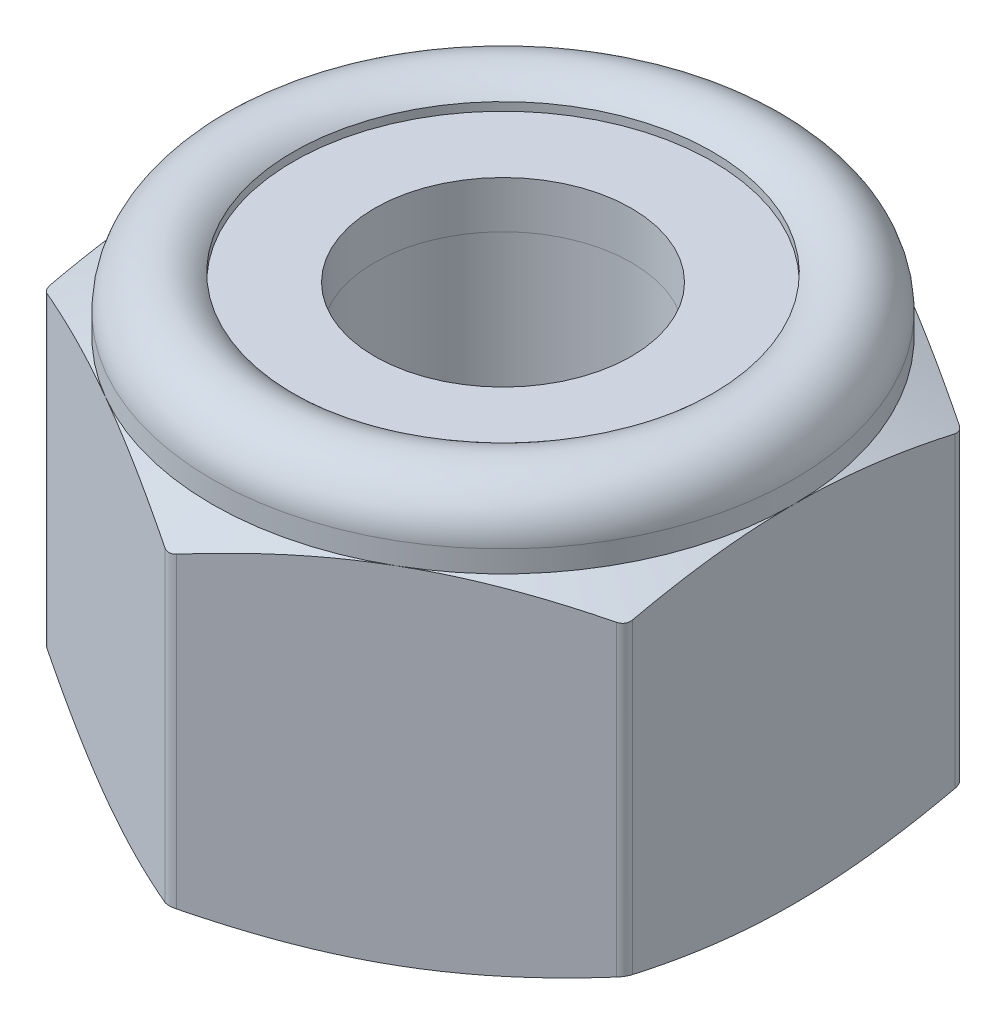
SolidWorks part; units mm, degrees
material "Plain Carbon Steel"
ref_plane "Front Plane" through (0, 0, 0) normal (0, 0, 1) x (1, 0, 0)
ref_plane "Top Plane" through (0, 0, 0) normal (0, 1, 0) x (1, 0, 0)
ref_plane "Right Plane" through (0, 0, 0) normal (1, 0, 0) x (0, 0, -1)
sketch "Sketch1" plane through (0, 0, 0) normal (0, 0, 1) x (1, 0, 0)
  line L0 (0, -2.5) -> (0, 2.5) construction
  line L1 (3.5, 0) -> (-3.5, 0) construction
  line L2 (2, -2.5) -> (-2, -2.5) construction
  line L3 (2, -2.5) -> (2, -1.8) construction
  point P4 (0, 0)
  point P8 (0, 0)
  point P11 (0, -2.5)
  dimension "Height" = 5
  dimension "Width" = 7
  dimension "Thread Size" = 4
  dimension "Thread Pitch" = 0.7
sketch "Sketch2" plane through (0, 0, 0) normal (0, 1, 0) x (1, 0, 0)
  line L0 (-2, 0.3063) -> (-2, -0.3063) construction
  line L1 (0, 4.0415) -> (-3.5, 2.0207)
  line L2 (-3.5, 2.0207) -> (-3.5, -2.0207)
  line L3 (-3.5, -2.0207) -> (0, -4.0415)
  line L4 (0, -4.0415) -> (3.5, -2.0207)
  line L5 (3.5, -2.0207) -> (3.5, 2.0207)
  line L6 (3.5, 2.0207) -> (0, 4.0415)
  line L7 (-2, -0.3063) -> (-1.5453, -0.0438) construction
  line L8 (-1.5453, -0.0438) -> (-1.5453, 0.0437) construction
  line L9 (-1.5453, 0.0437) -> (-2, 0.3063) construction
  line L10 (-1.5453, 0) -> (-2, 0) construction
  line L11 (-1.7727, 0.175) -> (-1.7727, -0.175) construction
  line L12 (2, 0) -> (-2, 0) construction
  line L13 (3.5, 0) -> (-3.5, 0) construction
  circle A0 centre (0, 0) radius 3.5 construction
  circle A1 centre (0, 0) radius 1.5453
  point P19 (0, -1.5453)
  dimension "D1" = 0.0875
  dimension "D2" = 0.35
  dimension "D3" = 60
extrude "Boss-Extrude1" add sketch "Sketch2" along normal up to vertex (2.5 mm away) and the other way up to vertex (2.5 mm away) up to point (0, 2.5, 0) other way up to point (0, -2.5, 0)
fillet "Fillet1" radius 0.14 6 edges at (-3.5, 0, -2.0207) (0, 0, -4.0415) (-3.5, 0, 2.0207) (3.5, 0, -2.0207) (3.5, 0, 2.0207) (0, 0, 4.0415)
sketch "Sketch3" plane through (0, 0, 0) normal (1, 0, 0) x (0, 0, -1)
  line L0 (4.0415, 1.6667) -> (4.0415, 3.5)
  line L2 (3.5, -2.5) -> (4.0415, -2.2475)
  line L3 (2.0611, -2.5) -> (4.001, -2.5) construction
  line L4 (4.0415, 2.5) -> (4.0415, -2.5) construction
  line L5 (4.0415, -2.2475) -> (4.0415, -2.5)
  line L6 (4.0415, -2.5) -> (3.5, -2.5)
  line L7 (3.5, 1.6667) -> (4.0415, 1.4142)
  line L8 (4.0415, 1.4142) -> (4.0415, 1.6667)
  line L11 (3.5, 1.6667) -> (3.5, 1.9275)
  line L12 (2.0611, 2.5) -> (4.001, 2.5) construction
  line L13 (1.5453, 1.6667) -> (2.5227, 1.6667)
  line L14 (2.5227, 1.6667) -> (2.5227, 2.3323)
  line L15 (2.5227, 1.6667) -> (3.5, 1.6667) construction
  line L16 (2.5227, 2.3323) -> (2.9275, 1.9275) construction
  line L17 (2.9275, 1.9275) -> (2.9275, 2.5) construction
  line L18 (1.5453, 1.6667) -> (1.5453, 3.5)
  line L19 (1.5453, 3.5) -> (4.0415, 3.5)
  line L21 (1.5453, -2.5) -> (1.5453, -2.1)
  line L22 (-1.9399, -2.5) -> (1.9399, -2.5) construction
  line L24 (1.9453, -2.5) -> (1.5453, -2.5)
  line L25 (1.5453, -2.1) -> (1.9453, -2.5)
  arc A0 (3.5, 1.9275) -> (2.5227, 2.3323) centre (2.9275, 1.9275) ccw
  point P0 (3.5, 1.6667)
  point P1 (3.5, 0)
  point P14 (1.5453, 0)
  dimension "D1" = 4.1667
  dimension "D2" = 25
  dimension "D3" = 45
  dimension "D5" = 0.4
revolve "Cut-Revolve2" cut sketch "Sketch3" angle 360 about L0
sketch "Sketch4" plane through (0, 0, 0) normal (1, 0, 0) x (0, 0, -1)
  line L0 (-2.5227, 2.3323) -> (-2.5227, 1.6667) construction
  line L1 (-1.5453, 1.6667) -> (-2.5227, 1.6667)
  line L2 (-1.5453, 1.6667) -> (-1.5453, 2.2323)
  line L3 (-1.5453, 2.2323) -> (-2.5227, 2.2323)
  line L4 (-2.5227, 1.6667) -> (-2.5227, 2.2323)
  line L5 (2.5227, 2.3323) -> (-2.5227, 2.3323) construction
  line L6 (1.5453, 1.6667) -> (-1.5453, 1.6667) construction
revolve "Revolve1" add sketch "Sketch4" angle 360 about L0
sketch "Sketch5" plane through (0, 0, 0) normal (0, 1, 0) x (1, 0, 0)
  circle A0 centre (0, 0) radius 1.5453 construction
  point P0 (0, -1.5453)
sketch "Sketch6" [suppressed] plane through (0, 0, 0) normal (0, 0, 1) x (1, 0, 0)
  line L0 (2, 1.6667) -> (2, -2.5)
  line L2 (0, -2.5) -> (3.5, -2.5) construction
  line L3 (2, -2.5) -> (0, -2.5)
  line L4 (0, -2.5) -> (0, 1.6667)
  line L5 (0, -2.5) -> (0, 2.5) construction
  line L6 (0, 1.6667) -> (2, 1.6667)
  line L7 (3.5, 1.6667) -> (1.75, 1.6667) construction
revolve "Revolve2" [suppressed] add sketch "Sketch6" angle 360 about L4
sketch "Sketch7" [suppressed] plane through (0, -2.5, 0) normal (0, -1, 0) x (1, 0, 0)
  circle A2 centre (0, 0) radius 2
  circle A3 centre (0, 0) radius 2
  dimension "D1" = 0
curve "Helix/Spiral1" [suppressed] pitch 0.7 height 5 turns 7.1429
sketch "Sketch8" [suppressed] plane through (0, 0, 0) normal (0, 0, 1) x (1, 0, 0)
  line L0 (2.0758, -2.4563) -> (1.4696, -2.8063) construction
  line L1 (1.4696, -2.8063) -> (2.0758, -3.1563) construction
  line L2 (2.0758, -3.1563) -> (2.0758, -2.4563) construction
  line L3 (1.5453, -2.7625) -> (1.5453, -2.85)
  line L4 (2, -2.5) -> (2, -3.1125) construction
  line L5 (2, -2.8063) -> (2.0758, -2.8063) construction
  line L6 (1.4696, -2.8063) -> (1.5453, -2.8063) construction
  line L7 (2.0379, -2.8063) -> (2.0379, -3.1344) construction
  line L8 (1.5453, -2.7625) -> (2.0758, -2.4563)
  line L9 (2.0758, -2.4563) -> (2.0379, -3.1344)
  line L10 (1.5453, -2.85) -> (2.0379, -3.1344)
  dimension "D1" = 0.7
  dimension "D2" = 0.0875
sweep "Cut-Sweep1" [suppressed] cut profiles "Sketch8" path "Helix/Spiral1"
sketch "Sketch9" [suppressed] plane through (0, 0, 0) normal (0, 0, 1) x (1, 0, 0)
  line L0 (0, -0.5) -> (0, -2.5)
  line L1 (0, -0.5) -> (0, -0.1)
  line L2 (0, -2.5) -> (2, -2.5)
  line L3 (2, -2.5) -> (2.4, -2.5)
  line L4 (2.4, -2.5) -> (0, -0.1)
revolve "Revolve3" [suppressed] add sketch "Sketch9" angle 360 about L0
sketch "Sketch10" [suppressed] plane through (0, -2.5, 0) normal (0, -1, 0) x (1, 0, 0)
  circle A0 centre (0, 0) radius 1.9453 construction
  circle A1 centre (0, 0) radius 1.9453
extrude "Boss-Extrude2" [suppressed] add sketch "Sketch10" against normal up to surface (4.1667 mm away)
combine bodies "Combine1" [suppressed] operation type subtract main body 110 bodies to subtract 109
equation "\"D1@Sketch3\"=\"Height@sketch1\"*(5/6)"
equation "\"D5@Sketch3\"=\"Thread Size@Sketch1\"*.1"
equation "\"D4@Helix/Spiral1\"=\"Thread Pitch@sketch1\""
equation "\"D3@Helix/Spiral1\"=\"Height@sketch1\""
equation "\"D1@Sketch8\"=\"Thread Pitch@sketch1\""
equation "\"D2@Sketch8\"=\"Thread Pitch@sketch1\"/8"
equation "\"D1@Sketch9\"=\"Thread Size@Sketch1\" * .1"
equation "\"D1@Sketch2\"=\"Thread Pitch@sketch1\"/8"
equation "\"D2@Sketch2\"=\"Thread Pitch@sketch1\"/2"
equation "\"D1@Sketch4\" = \"Height@Sketch1\" * .02"
equation "\"D1@Fillet1\"=\"Width@sketch1\"*.02"
